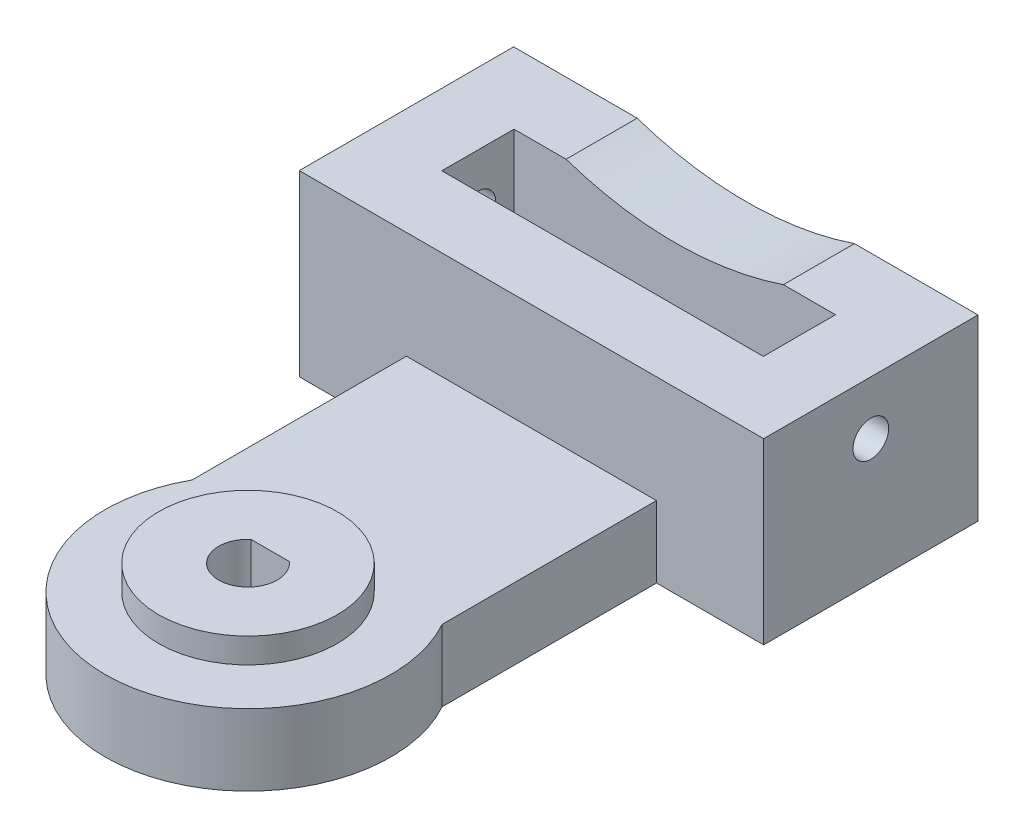
SolidWorks part; units mm, degrees
ref_plane "Front Plane" through (0, 0, 0) normal (0, 0, 1) x (1, 0, 0)
ref_plane "Top Plane" through (0, 0, 0) normal (0, 1, 0) x (1, 0, 0)
ref_plane "Right Plane" through (0, 0, 0) normal (1, 0, 0) x (0, 0, -1)
sketch "Sketch1" plane through (0, 0, 0) normal (0, 1, 0) x (1, 0, 0)
  circle A21 centre (0, 0) radius 20
  dimension "D1" = 40
extrude "Boss-Extrude1" add sketch "Sketch1" along normal blind 10
sketch "Sketch2" plane through (0, 10, 0) normal (0, 1, 0) x (1, 0, 0)
  line L0 (-2.6458, 3) -> (2.6458, 3) construction
  line L1 (-2.6833, 3.1) -> (2.6833, 3.1)
  arc A0 (-2.6458, 3) -> (2.6458, 3) centre (0, 0) ccw construction
  arc A1 (-2.6833, 3.1) -> (2.6833, 3.1) centre (0, 0) ccw
  point P3 (0, 3)
  dimension "D1" = 4
  dimension "D2" = 5.2915
  dimension "D3" = 0.1
extrude "Cut-Extrude1" cut sketch "Sketch2" against normal offset from surface (2.5 mm away) 7.5 up to face at (0, 0, 20)
sketch "Sketch3" plane through (0, 0, 0) normal (0, 1, 0) x (1, 0, 0)
  line L0 (-17.5, 59.6825) -> (-17.5, 9.6825)
  line L1 (-17.5, 59.6825) -> (17.5, 59.6825)
  line L2 (17.5, 59.6825) -> (17.5, 9.6825)
  circle A0 centre (0, 0) radius 20 construction
  arc A1 (17.5, 9.6825) -> (-17.5, 9.6825) centre (0, 0) ccw
  point P6 (0, 59.6825)
  point P9 (0, 20)
  dimension "D1" = 35
  dimension "D2" = 50
extrude "Boss-Extrude2" add sketch "Sketch3" along normal up to surface (10 mm away) up to face at (0, 10, 0.5)
sketch "Sketch6" plane through (0, 10, 0) normal (0, 1, 0) x (1, 0, 0)
  line L5 (-2.6833, 3.1) -> (2.6833, 3.1) construction
  line L6 (-2.6833, 3.1) -> (2.6833, 3.1)
  circle A0 centre (0, 0) radius 12.5
  arc A3 (-2.6833, 3.1) -> (2.6833, 3.1) centre (0, 0) ccw construction
  arc A4 (-2.6833, 3.1) -> (2.6833, 3.1) centre (0, 0) ccw
  dimension "D1" = 25
extrude "Boss-Extrude3" add sketch "Sketch6" along normal blind 6
sketch "Sketch7" plane through (0, 0, -59.6825) normal (0, 0, -1) x (-1, 0, 0)
  line L0 (-32.5, 0) -> (-32.5, 25)
  line L1 (-32.5, 25) -> (-22.5, 25)
  line L2 (-22.5, 25) -> (-22.5, 10)
  line L3 (-17.5, 10) -> (17.5, 10) construction
  line L4 (-22.5, 10) -> (22.5, 10)
  line L5 (22.5, 10) -> (22.5, 25)
  line L6 (22.5, 25) -> (32.5, 25)
  line L7 (32.5, 25) -> (32.5, 0)
  line L8 (32.5, 0) -> (-32.5, 0)
  dimension "D1" = 10
  dimension "D2" = 15
  dimension "D3" = 45
extrude "Boss-Extrude4" add sketch "Sketch7" against normal blind 20 and the other way blind 10
sketch "Sketch8" plane through (-32.5, 0, 0) normal (-1, 0, 0) x (0, 0, 1)
  line L1 (-39.6825, 25) -> (-69.6825, 25) construction
  circle A0 centre (-54.6825, 17.5) radius 2.5
  point P7 (-54.6825, 25)
  dimension "D2" = 5
  dimension "D1" = 7.5
extrude "Cut-Extrude2" cut sketch "Sketch8" against normal through all
sketch "Sketch9" plane through (0, 16, 0) normal (0, 1, 0) x (1, 0, 0)
  circle A0 centre (0, 0) radius 12.5
  circle A1 centre (0, 0) radius 12.5 construction
extrude "Cut-Extrude3" cut sketch "Sketch9" against normal blind 2.5
sketch "Sketch10" plane through (0, 0, -69.6825) normal (0, 0, -1) x (-1, 0, 0)
  line L1 (-22.5, 10) -> (22.5, 10)
  line L2 (-22.5, 10) -> (-22.5, 25)
  line L3 (-22.5, 25) -> (22.5, 25)
  line L4 (22.5, 10) -> (22.5, 25)
extrude "Boss-Extrude5" add sketch "Sketch10" against normal blind 9.95
sketch "Sketch11" plane through (0, 0, -39.6825) normal (0, 0, 1) x (1, 0, 0)
  line L1 (-22.5, 10) -> (22.5, 10)
  line L2 (-22.5, 10) -> (-22.5, 25)
  line L3 (-22.5, 25) -> (22.5, 25)
  line L4 (22.5, 10) -> (22.5, 25)
extrude "Boss-Extrude6" add sketch "Sketch11" against normal blind 9.95
sketch "Sketch12" plane through (0, 0, -69.6825) normal (0, 0, -1) x (-1, 0, 0)
  circle A0 centre (0, 70) radius 47.5
  point P2 (0, 0)
  point P4 (0, 40.9818)
  point P5 (0, 69.5913)
  dimension "D1" = 95
  dimension "D2" = 70
extrude "Cut-Extrude5" cut sketch "Sketch12" against normal blind 9.95
